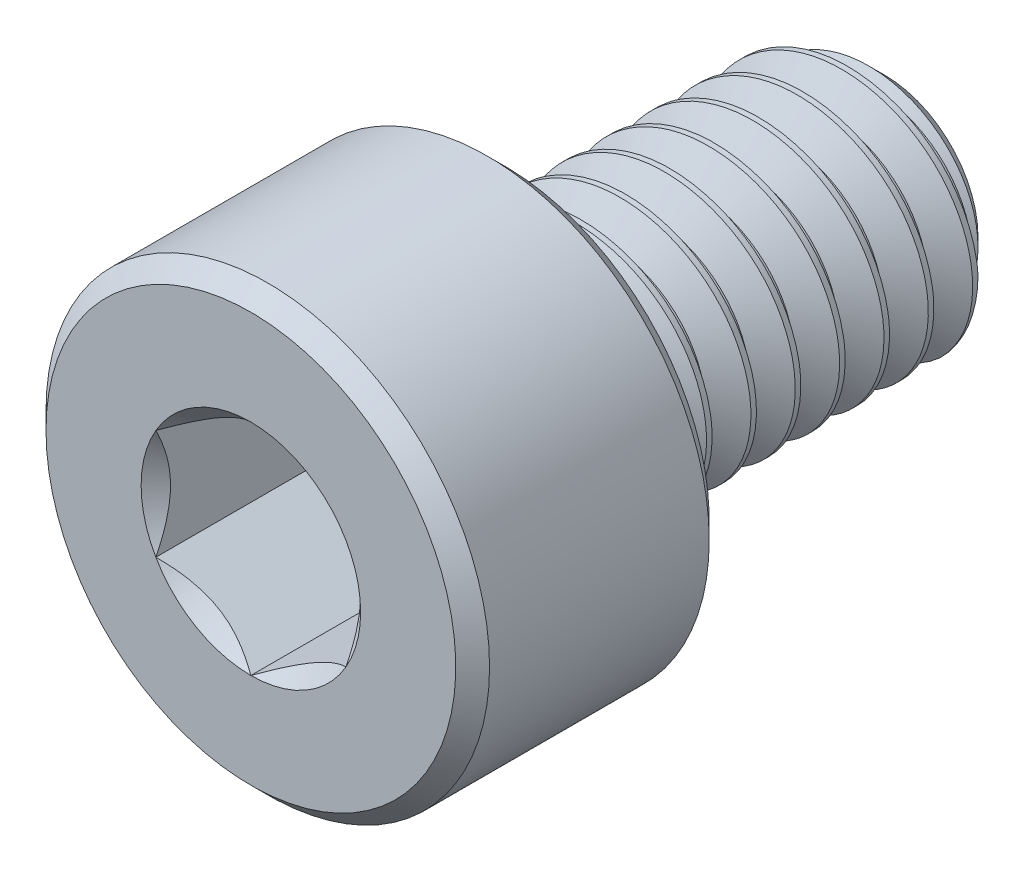
SolidWorks part; units mm, degrees
other "DetailItem1"
ref_plane "Front Plane" through (0, 0, 0) normal (0, 0, 1) x (1, 0, 0)
ref_plane "Top Plane" through (0, 0, 0) normal (0, 1, 0) x (1, 0, 0)
ref_plane "Right Plane" through (0, 0, 0) normal (1, 0, 0) x (0, 0, -1)
sketch "Sketch1" plane through (0, 0, 0) normal (1, 0, 0) x (0, 0, -1)
  line L0 (-5, 0) -> (5, 0) construction
  line L1 (-5, 3.5) -> (-5, -3.5) construction
  line L2 (-5, 3.5) -> (-1, 3.5) construction
  line L3 (-1, 3.5) -> (-1, 2) construction
  line L4 (-1, 2) -> (5, 2) construction
  line L5 (5, 2) -> (5, -2) construction
  line L6 (4.9563, 2.0758) -> (5.6563, 2.0758) construction
  line L7 (5.6563, 2.0758) -> (5.3063, 1.4696) construction
  line L8 (5.3063, 1.4696) -> (4.9563, 2.0758) construction
  line L9 (5.3063, 2.0758) -> (5.3063, 2) construction
  line L10 (5, 2) -> (5.6125, 2) construction
  line L11 (5.3063, 1.5453) -> (5.3063, 1.4696) construction
  line L12 (5.2625, 1.5453) -> (5.35, 1.5453) construction
  line L13 (4.9781, 2.0379) -> (5.6344, 2.0379) construction
  line L14 (-2, 1.5) -> (-2, -1.5) construction
  point P10 (5, 0)
  point P18 (5.3063, 2.0379)
  point P21 (-2, 0)
  point P24 (2.9, 2)
  dimension "Head Diameter" = 7
  dimension "Thread size" = 4
  dimension "Head Height" = 4
  dimension "Pitch" = 0.7
  dimension "D1" = 0.0875
  dimension "Drive Size" = 3
  dimension "D2" = 3
  dimension "D3" = 2.1
  dimension "Length" = 6
sketch "Sketch2" plane through (0, 0, 0) normal (1, 0, 0) x (0, 0, -1)
  line L0 (-5, 0) -> (-5, 3.2333)
  line L1 (-5, 3.5) -> (-5, -3.5) construction
  line L2 (-5, 3.2333) -> (-4.7333, 3.5)
  line L3 (-5, 3.5) -> (-1, 3.5) construction
  line L4 (-4.7333, 3.5) -> (-1.2667, 3.5)
  line L5 (-1.2667, 3.5) -> (-1, 3.2333)
  line L6 (-1, 3.5) -> (-1, 2) construction
  line L7 (-1, 3.2333) -> (-1, 2)
  line L8 (-1, 2) -> (4.475, 2)
  line L9 (-1, 2) -> (5, 2) construction
  line L10 (4.475, 2) -> (5, 1.475)
  line L11 (5, 2) -> (5, -2) construction
  line L12 (5, 1.475) -> (5, 0)
  line L13 (5, 0) -> (-5, 0)
  dimension "D1" = 0.2667
  dimension "D2" = 45
  dimension "D3" = 45
  dimension "D4" = 0.525
revolve "Revolve1" add sketch "Sketch2" angle 360 about L13
sketch "Sketch3" plane through (0, 0, 5) normal (0, 0, 1) x (1, 0, 0)
  line L1 (0, 1.7321) -> (-1.5, 0.866)
  line L2 (-1.5, 0.866) -> (-1.5, -0.866)
  line L3 (-1.5, -0.866) -> (0, -1.7321)
  line L4 (0, -1.7321) -> (1.5, -0.866)
  line L5 (1.5, -0.866) -> (1.5, 0.866)
  line L6 (1.5, 0.866) -> (0, 1.7321)
  circle A0 centre (0, 0) radius 1.5 construction
extrude "Cut-Extrude1" cut sketch "Sketch3" against normal up to vertex (3 mm away) up to point (0, 1.5, 2)
sketch "Sketch4" plane through (0, 0, 5) normal (0, 0, 1) x (1, 0, 0)
  circle A0 centre (0, 0) radius 1.7321
extrude "Cut-Extrude2" cut sketch "Sketch4" against normal through all draft 45
split "Split1" bodies to split 113 resulting bodies 114 115 split by face at (-3.2333, 0, 1)
sketch "Sketch5" plane through (0, 0, -5) normal (0, 0, -1) x (-1, 0, 0)
  circle A0 centre (0, 0) radius 2
  circle A1 centre (0, 0) radius 1.475 construction
curve "Helix/Spiral1" pitch 0.7 height 6.7 radius 2 centre (0, 0, -5) axis (0, 0, 1) start towards (0, 1, 0)
sketch "Sketch6" plane through (0, 0, 0) normal (1, 0, 0) x (0, 0, -1)
  line L0 (4.9781, 2.0379) -> (5.6344, 2.0379)
  line L1 (5.6344, 2.0379) -> (5.35, 1.5453)
  line L2 (5.35, 1.5453) -> (5.2625, 1.5453)
  line L3 (5.2625, 1.5453) -> (4.9781, 2.0379)
sweep "Cut-Sweep1" cut profiles "Sketch6" path "Helix/Spiral1" align with end faces yes
sketch "Sketch7" plane through (0, 0, 1) normal (0, 0, -1) x (-1, 0, 0)
  circle A0 centre (0, 0) radius 2
extrude "Boss-Extrude2" add sketch "Sketch7" along normal up to next (6 mm away) draft 20
equation "\"D1\"= \"hex dia@Sketch7\" * .75"
equation "\"D1@Sketch1\"=\"Pitch@Sketch1\"/8"
equation "\"D2@Sketch1\"=\"Drive Size@Sketch1\""
equation "\"D1@Sketch2\"=\"Head Height@Sketch1\"/15"
equation "\"D4@Sketch2\"=\"Pitch@Sketch1\"*.75"
equation "\"D4@Helix/Spiral1\"=\"Pitch@Sketch1\""
equation "\"D3@Helix/Spiral1\"=\"Length@Sketch1\"+\"Pitch@Sketch1\""
equation "\"D3@Sketch1\"=\"Pitch@Sketch1\"*3"
